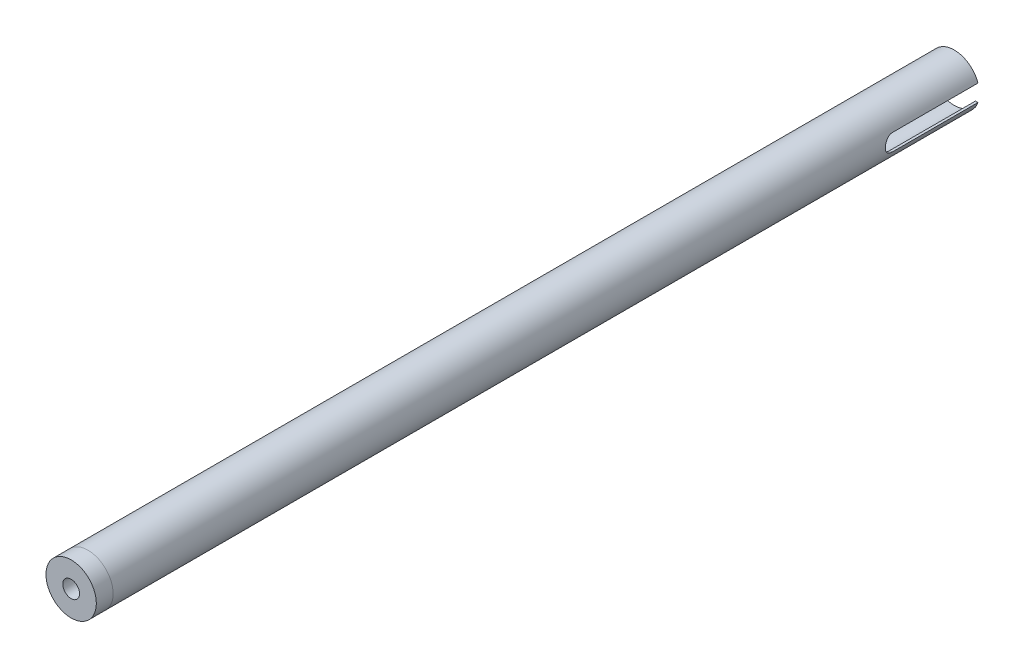
SolidWorks part; units mm, degrees
material "AISI 4130 Steel, normalized at 870C"
ref_plane "Front Plane" through (0, 0, 0) normal (0, 0, 1) x (1, 0, 0)
ref_plane "Top Plane" through (0, 0, 0) normal (0, 1, 0) x (1, 0, 0)
ref_plane "Right Plane" through (0, 0, 0) normal (1, 0, 0) x (0, 0, -1)
sketch "Axis" plane through (0, 0, 0) normal (0, 1, 0) x (1, 0, 0)
  line L0 (0, 0) -> (0, 333.8909) construction
  line L1 (0, 0) -> (0, -21.59) construction
  line L2 (0, 333.8909) -> (-9.525, 333.8909) construction
  line L4 (0, 368.3926) -> (-10.3188, 331.0158) construction
  dimension "D1" = 21.59
  dimension "D2" = 9.525
sketch "Sketch1" plane through (0, 0, 0) normal (0, 0, 1) x (1, 0, 0)
  line L0 (-9.525, 0) -> (9.525, 0) construction
  line L1 (-8.9803, 3.175) -> (8.9803, 3.175)
  line L2 (-8.9803, -3.175) -> (8.9803, -3.175)
  circle A0 centre (0, 0) radius 9.525
  circle A1 centre (0, 0) radius 8.636
  circle A2 centre (0, 0) radius 3.175
  dimension "D1" = 19.05
  dimension "D3" = 6.35
  dimension "D2" = 0.889
  dimension "D4" = 6.35
extrude "Threaded insert 1-1" add sketch "Sketch1" against normal blind 6.35 contours A2 L1 A1 | A1 L1 A0 | A2 L0 A1 L1 | A1 L0 A0 L1 | L0 A1 L2 A0 | L0 A2 L2 A1 | A2 L2 A1 | A1 L2 A0 | L0 A1 L2 A2 | L0 A0 L2 A1 | A0 L0 A1 L1 | A1 L0 A2 L1 region at (5.4259, 1.6615, 0) region at (5.4259, -1.6615, 0) region at (8.8881, 1.6046, 0) region at (8.8881, -1.6046, 0) region at (-5.4259, -1.6615, 0) region at (-5.4259, 1.6615, 0) region at (0, 5.4321, 0) region at (0, -5.4321, 0) region at (0, 8.8265, 0) region at (8.5057, -3.3655, 0) region at (-8.8881, -1.6046, 0) region at (-8.8881, 1.6046, 0)
extrude "Threaded insert 1-2" add sketch "Sketch1<3>" against normal blind 6.35 from surface contours A2 L1 A1 | A2 L0 A1 L1 | L0 A2 L2 A1 | A2 L2 A1 | L0 A1 L2 A2 | A1 L0 A2 L1 region at (5.4259, 1.6615, 0) region at (5.4259, -1.6615, 0) region at (-5.4259, -1.6615, 0) region at (-5.4259, 1.6615, 0) region at (0, 5.4321, 0) region at (0, -5.4321, 0) starting at face at (9.525, 0, -6.35)
sketch "Sketch1<3>" plane through (0, 0, 0) normal (0, 0, 1) x (1, 0, 0) same geometry as "Sketch1"
extrude "A-arm tube" add sketch "Sketch1<4>" against normal up to vertex (333.8909 mm away) from surface separate body contours A1 L1 A0 | A1 L0 A0 L1 | L0 A1 L2 A0 | A1 L2 A0 | L0 A0 L2 A1 | A0 L0 A1 L1 region at (8.8881, 1.6046, 0) region at (8.8881, -1.6046, 0) region at (0, 8.8265, 0) region at (8.5057, -3.3655, 0) region at (-8.8881, -1.6046, 0) region at (-8.8881, 1.6046, 0) up to point (0, 0, -333.8909) starting at face at (8.636, 0, -6.35)
sketch "Sketch1<4>" plane through (0, 0, 0) normal (0, 0, 1) x (1, 0, 0) same geometry as "Sketch1"
extrude "Apex slot" cut sketch "Sketch1<5>" along normal blind 35.56 from surface contours A0 L0 A1 L1 | L0 A0 L2 A1 | A1 L0 A0 L1 | L0 A1 L2 A0 region at (8.8881, 1.6046, 0) region at (8.8881, -1.6046, 0) region at (-8.8881, -1.6046, 0) region at (-8.8881, 1.6046, 0) starting at face at (8.636, 0, -333.8909)
sketch "Sketch1<5>" plane through (0, 0, 0) normal (0, 0, 1) x (1, 0, 0) same geometry as "Sketch1"
fillet "Fillet1" radius 3.175 4 edges at (-8.5057, 3.175, -298.3309) (-8.5057, -3.175, -298.3309) (8.5057, -3.175, -298.3309) (8.5057, 3.175, -298.3309)
equation "\"tube diameter\"= 3 / 4"
equation "\"tube thickness\"= .035"
equation "\"apex thickness\"= .25"
equation "\"tube slot\"= 1.4"
equation "\"D1@Sketch1\"=\"tube diameter\""
equation "\"D2@Sketch1\"=\"tube thickness\""
equation "\"threaded insert hole\"= 1 / 4"
equation "\"D3@Sketch1\"=\"threaded insert hole\""
equation "\"D4@Sketch1\"=\"apex thickness\""
equation "\"D1@Apex slot\" = \"tube slot\""
equation "\"D1@Fillet1\"=\"apex thickness\"/2"
equation "\"D2@Axis\"=\"tube diameter\"/2"
